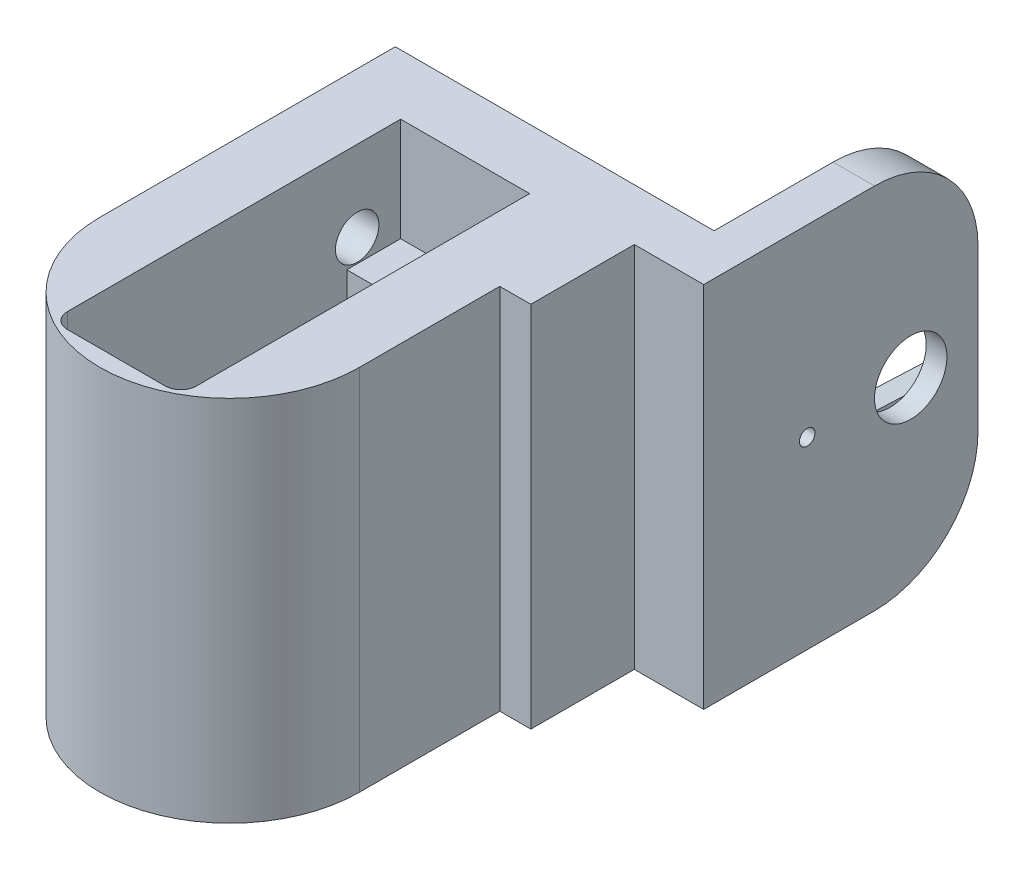
SolidWorks part; units mm, degrees
ref_plane "Front Plane" through (0, 0, 0) normal (0, 0, 1) x (1, 0, 0)
ref_plane "Top Plane" through (0, 0, 0) normal (0, 1, 0) x (1, 0, 0)
ref_plane "Right Plane" through (0, 0, 0) normal (1, 0, 0) x (0, 0, -1)
sketch "Sketch4" plane through (0, 0, 0) normal (0, 0, 1) x (1, 0, 0)
  line L1 (-6.23, -9.975) -> (6.23, -9.975)
  line L2 (-6.23, -9.975) -> (-6.23, 7.275)
  line L3 (-6.23, 7.275) -> (6.23, 7.275)
  line L4 (6.23, -9.975) -> (6.23, 7.275)
  point P4 (0, 7.275)
  dimension "D1" = 12.46
  dimension "D2" = 17.25
  dimension "D3" = 9.975
extrude "Boss-Extrude3" add sketch "Sketch4" along normal blind 6
sketch "Sketch8" plane through (0, -9.975, 0) normal (0, -1, 0) x (-1, 0, 0)
  circle A0 centre (0, -23.55) radius 12.5468
  circle A1 centre (0, -23.55) radius 11.15
  dimension "D1" = 22.3
  dimension "D2" = 23.55
extrude "Boss-Extrude6" add sketch "Sketch8" along normal blind 8.3 and the other way up to surface (17.25 mm away) other way up to face at (0, 7.275, 3)
sketch "Sketch5" plane through (0, 7.275, 0) normal (0, 1, 0) x (1, 0, 0)
  line L8 (12.5468, -23.55) -> (12.5468, 0)
  line L9 (12.5468, 0) -> (6.23, 0)
  line L10 (-12.5468, -23.55) -> (-12.5468, 0)
  line L11 (-12.5468, 0) -> (-6.23, 0)
  line L12 (-6.23, 0) -> (-6.23, -29.7)
  line L14 (6.23, -29.7) -> (6.23, 0)
  line L15 (-6.23, -29.7) -> (6.23, -29.7)
  line L16 (6.23, -6) -> (-6.23, -6) construction
  circle A0 centre (0, -23.55) radius 12.5468 construction
  arc A1 (-12.5468, -23.55) -> (12.5468, -23.55) centre (0, -23.55) ccw
  dimension "D1" = 23.7
  dimension "D2" = 23.55
extrude "Boss-Extrude4" add sketch "Sketch5" against normal up to surface (17.25 mm away) up to face at (0, -9.975, 3)
sketch "Sketch6" plane through (0, 7.275, 0) normal (0, 1, 0) x (1, 0, 0)
  line L0 (6.23, -6) -> (-6.23, -6) construction
  line L3 (6.23, -29.7) -> (-6.23, -29.7) construction
  circle A0 centre (0, -3.6) radius 0.75
  circle A1 centre (0, -32.1) radius 0.75
  dimension "D1" = 1.5
  dimension "D3" = 1.5
  dimension "D2" = 2.4
  dimension "D4" = 2.4
extrude "Cut-Extrude1" cut sketch "Sketch6" against normal blind 5
chamfer "Chamfer1" distance 0.5 angle 60 2 edges at (0, 7.275, 4.35) (0, 7.275, 32.85) first distance on face at (0, 7.275, 4.35)
sketch "Sketch10" plane through (0, 7.275, 0) normal (0, 1, 0) x (1, 0, 0)
  line L1 (-6.23, -6) -> (6.23, -6)
  line L2 (-6.23, -6) -> (-6.23, -29.7)
  line L3 (-6.23, -29.7) -> (6.23, -29.7)
  line L4 (6.23, -6) -> (6.23, -29.7)
extrude "Cut-Extrude3" cut sketch "Sketch10" against normal up to surface (17.25 mm away) up to face at (0, -9.975, 27.1007)
ref_plane "Plane1" through (0, 0, 36.0968) normal (0, 0, 1) x (1, 0, 0)
sketch "Sketch13" plane through (0, -18.275, 0) normal (0, -1, 0) x (1, 0, 0)
  line L0 (-12.5468, 23.55) -> (-12.5468, 0)
  line L1 (-12.5468, 0) -> (12.5468, 0)
  line L2 (12.5468, 0) -> (12.5468, 23.55)
  arc A0 (-12.5468, 23.55) -> (12.5468, 23.55) centre (0, 23.55) ccw
  point P3 (0, 0)
extrude "Boss-Extrude7" add sketch "Sketch13" against normal up to surface (8.3 mm away) up to face at (0, -9.975, 27.1007)
sketch "Sketch15" plane through (0, 7.275, 0) normal (0, 1, 0) x (1, 0, 0)
  line L0 (-12.5468, 0) -> (12.5468, 0)
  line L1 (12.5468, 0) -> (12.5468, -23.55)
  line L2 (-12.5468, 0) -> (-12.5468, -23.55)
  line L3 (6.23, -6) -> (6.23, -29.7) construction
  line L4 (-6.23, -0.8) -> (6.23, -0.8)
  line L5 (-6.23, -0.8) -> (-6.23, -33)
  line L6 (-4.73, -34.5) -> (4.73, -34.5)
  line L7 (6.23, -0.8) -> (6.23, -33)
  arc A0 (-12.5468, -23.55) -> (12.5468, -23.55) centre (0, -23.55) ccw
  circle A1 centre (0, -3.6) radius 0.75 construction
  arc A2 (4.73, -34.5) -> (6.23, -33) centre (4.73, -33) ccw
  arc A3 (-6.23, -33) -> (-4.73, -34.5) centre (-4.73, -33) ccw
  point P15 (0, -0.8)
  dimension "D1" = 0.8
  dimension "D3" = 1.5
  dimension "D2" = 2.8
  dimension "D4" = 0
  dimension "D5" = 34.5
extrude "Boss-Extrude9" add sketch "Sketch15" along normal blind 10
sketch "Sketch20" plane through (0, -18.275, 0) normal (0, -1, 0) x (1, 0, 0)
  circle A0 centre (0, 23.55) radius 7.15
  circle A1 centre (0, 23.55) radius 11.15
  circle A2 centre (0, 23.55) radius 11.15 construction
  dimension "D1" = 14.3
extrude "Boss-Extrude11" add sketch "Sketch20" against normal up to surface (8.3 mm away) up to face at (0, -9.975, 27.1007)
sketch "Sketch21" plane through (0, -18.275, 0) normal (0, -1, 0) x (1, 0, 0)
  circle A0 centre (0, 23.55) radius 7.15
  circle A1 centre (0, 23.55) radius 10.15
  circle A2 centre (0, 23.55) radius 7.15 construction
  dimension "D1" = 20.3
extrude "Cut-Extrude7" cut sketch "Sketch21" against normal blind 1.3
sketch "Sketch11" plane through (0, 0, 29.7) normal (0, 0, 1) x (1, 0, 0)
  line L1 (-5, -9.975) -> (5, -9.975)
  line L2 (-5, -9.975) -> (-5, -11.975)
  line L3 (-5, -11.975) -> (5, -11.975)
  line L4 (5, -9.975) -> (5, -11.975)
  line L5 (-3.6469, -9.975) -> (3.6469, -9.975) construction
  point P4 (0, -9.975)
  dimension "D1" = 0
  dimension "D2" = 10
  dimension "D3" = 2
extrude "Cut-Extrude4" cut sketch "Sketch11" against normal up to surface (23.7 mm away) up to face at (0, -1.35, 6)
sketch "Sketch25" plane through (0, -18.275, 0) normal (0, -1, 0) x (1, 0, 0)
  line L0 (6.23, 20.0415) -> (6.23, 6) construction
  line L1 (-6.23, 6) -> (6.23, 6)
  line L2 (-6.23, 6) -> (-6.23, 12)
  line L3 (-6.23, 12) -> (6.23, 12)
  line L4 (6.23, 6) -> (6.23, 12)
  dimension "D1" = 6
extrude "Cut-Extrude8" cut sketch "Sketch25" against normal up to next
sketch "Sketch17" plane through (0, 17.275, 0) normal (0, 1, 0) x (1, 0, 0)
  line L0 (22.25, 26.5) -> (22.25, 0)
  line L1 (22.25, 0) -> (-22.25, 0)
  line L2 (-22.25, 0) -> (-22.25, 26.5)
  line L3 (-22.25, 26.5) -> (-18.25, 26.5)
  line L4 (-18.25, 26.5) -> (-18.25, 5)
  line L5 (-18.25, 5) -> (18.25, 5)
  line L6 (18.25, 5) -> (18.25, 26.5)
  line L7 (18.25, 26.5) -> (22.25, 26.5)
  point P2 (0, 5)
  point P10 (0, 0)
  dimension "D1" = 4
  dimension "D2" = 36.5
  dimension "D3" = 0
  dimension "D4" = 26.5
  dimension "D5" = 5
extrude "Boss-Extrude10" add sketch "Sketch17" against normal up to surface (35.55 mm away) up to face at (0, -18.275, 9)
sketch "Sketch18" plane through (18.25, 0, 0) normal (-1, 0, 0) x (0, 0, 1)
  line L0 (-26.5, -18.275) -> (-26.5, 17.275) construction
  line L1 (-26.5, 5.2191) -> (-5, 5.2191)
  line L2 (-26.5, 5.2191) -> (-26.5, -6.2191)
  line L3 (-26.5, -6.2191) -> (-5, -6.2191)
  line L4 (-5, 5.2191) -> (-5, -6.2191)
  line L5 (-5, -18.275) -> (-5, 17.275) construction
  point P6 (-26.5, -0.5)
  point P7 (-26.5, -0.5)
  dimension "D1" = 0
extrude "Cut-Extrude5" cut sketch "Sketch18" against normal blind 2
sketch "Sketch19" plane through (20.25, 0, 0) normal (-1, 0, 0) x (0, 0, 1)
  line L0 (-26.5, -18.275) -> (-26.5, 17.275) construction
  circle A0 centre (-20, -0.5) radius 3.5
  point P4 (-26.5, -0.5)
  dimension "D1" = 7
  dimension "D2" = 6.5
  dimension "D3" = 0
extrude "Cut-Extrude6" cut sketch "Sketch19" against normal through all both and the other way through all
fillet "Fillet1" radius 10 4 edges at (20.25, -18.275, -26.5) (20.25, 17.275, -26.5) (-20.25, 17.275, -26.5) (-20.25, -18.275, -26.5)
ref_plane "Plane2" through (0, 0, 0) normal (1, 0, 0) x (0, 0, -1)
ref_plane "Plane3" through (0, -0.5, 0) normal (0, -1, 0) x (-1, 0, 0)
sketch "Sketch22" plane through (-22.25, 0, 0) normal (-1, 0, 0) x (0, 0, 1)
  circle A0 centre (-20, -0.5) radius 6.5
  dimension "D1" = 13
extrude "Boss-Extrude12" add sketch "Sketch22" against normal blind 5
sketch "Sketch23" plane through (-17.25, 0, 0) normal (1, 0, 0) x (0, 0, -1)
  circle A0 centre (20, -0.5) radius 5.85
  dimension "D1" = 11.7
extrude "Boss-Extrude13" add sketch "Sketch23" along normal blind 5
fillet "Fillet2" radius 1 1 edges at (-12.25, -0.5, -25.85)
sketch "Sketch26" plane through (20.25, 0, 0) normal (-1, 0, 0) x (0, 0, 1)
  line L0 (-5, 2) -> (-20, 2.6585)
  line L1 (-5, -18.275) -> (-5, 17.275) construction
  line L4 (-5, 5.2191) -> (-5, 2)
  line L6 (-26.5, 5.2191) -> (-5, 5.2191)
  line L7 (-20, -3.6585) -> (-5, -3)
  line L8 (-5, -3) -> (-5, -6.2191)
  line L9 (-24.475, -0.5) -> (24.475, -0.5) construction
  line L11 (-26.5, -6.2191) -> (-5, -6.2191)
  line L12 (-20, 2.6585) -> (-26.5, 2.9439)
  line L13 (-20, -3.6585) -> (-26.5, -3.9438)
  line L14 (-26.5, -3.9438) -> (-26.5, -6.2191)
  line L16 (-26.5, 2.9439) -> (-26.5, 5.2191)
  line L18 (-26.5, -8.275) -> (-26.5, 7.275) construction
  circle A0 centre (-20, -0.5) radius 3.5 construction
  dimension "D1" = 5
  dimension "D2" = 2.5
  dimension "D3" = 0
  dimension "D4" = 6.317
  dimension "D5" = 3.1585
  dimension "D6" = 180
  dimension "D7" = 180
extrude "Boss-Extrude14" add sketch "Sketch26" along normal up to surface (2 mm away) up to face at (18.25, 10.8669, -16.3142)
sketch "Sketch27" plane through (22.25, 0, 0) normal (1, 0, 0) x (0, 0, -1)
  line L0 (-24.475, -0.5) -> (24.475, -0.5) construction
  circle A0 centre (10, -0.5) radius 0.75
  circle A1 centre (20, -0.5) radius 3.5 construction
  dimension "D2" = 1.5
  dimension "D1" = 10
extrude "Cut-Extrude9" cut sketch "Sketch27" against normal up to next
sketch "Sketch28" plane through (0, -18.275, 0) normal (0, -1, 0) x (1, 0, 0)
  line L0 (-12.5468, 23.55) -> (-12.5468, -11.5534)
  line L5 (-12.5468, -11.5534) -> (-1.7209, -11.5534)
  line L6 (-1.7209, -11.5534) -> (-1.7209, -30.3021)
  line L7 (-1.7209, -30.3021) -> (-26.8097, -30.3021)
  line L8 (-26.8097, -30.3021) -> (-26.8097, 23.55)
  line L9 (-26.8097, 23.55) -> (-12.5468, 23.55)
extrude "Cut-Extrude10" cut sketch "Sketch28" against normal through all
sketch "Sketch29" plane through (-12.5468, 0, 0) normal (-1, 0, 0) x (0, 0, 1)
  line L0 (-5, 17.275) -> (-5, -18.275) construction
  line L3 (-26.5, 2.9438) -> (-26.5, -3.9438) construction
  circle A0 centre (5, 9.5) radius 2.1
  circle A1 centre (5, -10.5) radius 2.1
  circle A2 centre (5, -0.5) radius 3.2
  point P12 (-26.5, -0.5)
  dimension "D1" = 4.2
  dimension "D2" = 4.2
  dimension "D6" = 6.4
  dimension "D3" = 20
  dimension "D4" = 10
  dimension "D7" = 10
extrude "Cut-Extrude11" cut sketch "Sketch29" against normal blind 7
fillet "Fillet3" radius 1 2 edges at (-12.5468, -10.5, 7.1) (-12.5468, 9.5, 7.1)
sketch "Sketch31" plane through (12.5468, 0, 0) normal (1, 0, 0) x (0, 0, -1)
  line L0 (0, -18.275) -> (-23.55, -18.275) construction
  line L1 (0, 17.275) -> (-10, 17.275)
  line L2 (0, 17.275) -> (0, -18.275)
  line L3 (0, -18.275) -> (-10, -18.275)
  line L4 (-10, 17.275) -> (-10, -18.275)
  dimension "D1" = 10
extrude "Boss-Extrude15" add sketch "Sketch31" along normal blind 3
